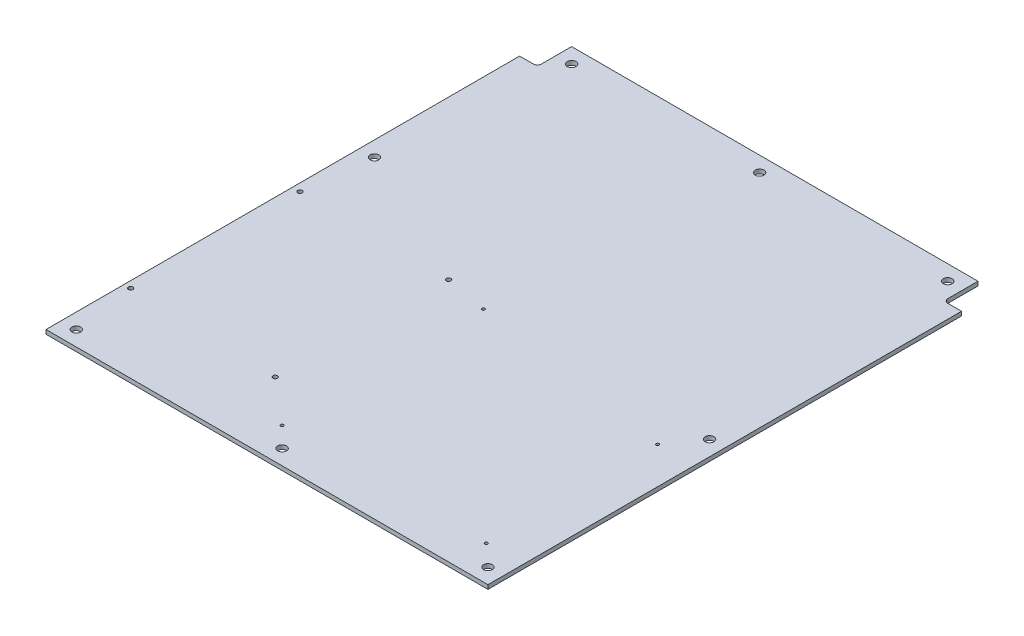
SolidWorks part; units mm, degrees
material "6061-T6 (SS)"
ref_plane "Front" through (0, 0, 0) normal (0, 0, 1) x (1, 0, 0)
ref_plane "Top" through (0, 0, 0) normal (0, 1, 0) x (1, 0, 0)
ref_plane "Right" through (0, 0, 0) normal (1, 0, 0) x (0, 0, -1)
sketch "Sketch1" plane through (0, 0, 0) normal (0, 1, 0) x (1, 0, 0)
  line L1 (170.434, -195.834) -> (-170.434, -195.834)
  line L2 (170.434, -195.834) -> (170.434, 195.834)
  line L3 (170.434, 195.834) -> (-170.434, 195.834)
  line L4 (-170.434, -195.834) -> (-170.434, 195.834)
  line L5 (170.434, -195.834) -> (-170.434, 195.834) construction
  line L6 (170.434, 195.834) -> (-170.434, -195.834) construction
  point P0 (0, 0)
  dimension "D1" = 340.868
  dimension "D2" = 391.668
extrude "Boss-Extrude1" add sketch "Sketch1" along normal blind 3.175
sketch "Sketch2" plane through (0, 3.175, 0) normal (0, 1, 0) x (1, 0, 0)
  line L0 (170.434, 195.834) -> (-170.434, 195.834) construction
  line L1 (-170.434, 195.834) -> (-156.718, 195.834)
  line L2 (-170.434, 195.834) -> (-170.434, 169.418)
  line L3 (-170.434, 169.418) -> (-159.893, 169.418)
  line L4 (-156.718, 195.834) -> (-156.718, 172.593)
  line L5 (170.434, 195.834) -> (156.718, 195.834)
  line L6 (170.434, 195.834) -> (170.434, 169.418)
  line L7 (170.434, 169.418) -> (159.893, 169.418)
  line L8 (156.718, 195.834) -> (156.718, 172.593)
  arc A0 (-156.718, 172.593) -> (-159.893, 169.418) centre (-159.893, 172.593) cw
  arc A1 (156.718, 172.593) -> (159.893, 169.418) centre (159.893, 172.593) ccw
  dimension "D1" = 3.175
  dimension "D2" = 26.416
  dimension "D3" = 13.716
extrude "Cut-Extrude1" cut sketch "Sketch2" against normal blind 10
hole_wizard "1/4 Clearance Hole1" positions "Sketch3" profile "Sketch4" hole size "1/4" standard "ANSI Inch"
sketch "Sketch3" plane through (0, 3.175, 0) normal (0, 1, 0) x (1, 0, 0)
  line L0 (158.75, -184.15) -> (0, -184.15) construction
  line L1 (0, -184.15) -> (-158.75, -184.15) construction
  line L2 (-158.75, -184.15) -> (-158.75, -13.208) construction
  line L3 (-158.75, -13.208) -> (-158.75, 157.734) construction
  line L4 (-158.75, 157.734) -> (158.75, 157.734) construction
  line L5 (158.75, 157.734) -> (158.75, -13.208) construction
  line L6 (158.75, -13.208) -> (158.75, -184.15) construction
  line L8 (145.034, 184.15) -> (0, 184.15) construction
  line L9 (0, 184.15) -> (-145.034, 184.15) construction
  line L10 (-145.034, 184.15) -> (-156.718, 195.834) construction
  line L12 (156.718, 195.834) -> (145.034, 184.15) construction
  line L14 (-158.75, 157.734) -> (-170.434, 169.418) construction
  line L16 (-158.75, -184.15) -> (-170.434, -195.834) construction
  line L18 (158.75, 157.734) -> (170.434, 169.418) construction
  line L20 (158.75, -184.15) -> (170.434, -195.834) construction
  line L21 (158.75, -184.15) -> (158.75, -195.834) construction
  line L22 (-170.434, -195.834) -> (170.434, -195.834) construction
  line L24 (158.75, -184.15) -> (170.434, -184.15) construction
  line L25 (170.434, -195.834) -> (170.434, 169.418) construction
  line L26 (156.718, 195.834) -> (-156.718, 195.834) construction
  point P0 (158.75, -184.15)
  point P2 (-158.75, -184.15)
  point P12 (158.75, -13.208)
  point P14 (0, -184.15)
  point P18 (0, 184.15)
  point P94 (-145.034, 184.15)
  point P96 (145.034, 184.15)
  point P104 (-158.75, 45.834)
  point P107 (0, 0)
  dimension "D1" = 11.684
  dimension "D2" = 150
sketch "Sketch4" plane through (158.75, 3.175, 184.15) normal (1, 0, 0) x (0, 0, 1)
  line L0 (0, 0) -> (0, 20.7798)
  line L1 (0, 20.7798) -> (3.3782, 18.75)
  line L2 (3.3782, 18.75) -> (3.3782, 0)
  line L5 (3.3782, 0) -> (0, 0)
  line L10 (0, 20.7798) -> (-3.3782, 18.75) construction
  line L11 (0, -6.35) -> (0, 107.95) construction
  dimension "Hole Dia." = 6.7564
  dimension "Hole Depth" = 18.75
  dimension "Drill Angle" = 118
hole_wizard "#4-40 Tapped Hole1" positions "Sketch5" profile "Sketch6" tap size "#4-40" standard "ANSI Inch"
sketch "Sketch5" plane through (0, 3.175, 0) normal (0, 1, 0) x (1, 0, 0)
  point P0 (-15.34, -13.51)
  point P3 (142.14, -36.73)
  point P6 (142.14, -168.81)
  point P9 (-15.34, -168.81)
sketch "Sketch6" plane through (-15.34, 3.175, 13.51) normal (1, 0, 0) x (0, 0, 1)
  line L0 (0, 0) -> (0, 8.2792)
  line L1 (0, 8.2792) -> (1.1303, 7.6)
  line L2 (1.1303, 7.6) -> (1.1303, 0)
  line L5 (1.1303, 0) -> (0, 0)
  line L10 (0, 8.2792) -> (-1.1303, 7.6) construction
  line L11 (0, -6.35) -> (0, 107.95) construction
  dimension "Tap Drill Dia." = 2.2606
  dimension "Tap Drill Depth" = 7.6
  dimension "Drill Angle" = 118
cosmetic thread "Hole Thread1" parameters "D1"=3.175, "D2"=2.8448
cosmetic thread "Hole Thread2" parameters "D1"=3.175, "D2"=2.8448
cosmetic thread "Hole Thread3" parameters "D1"=3.175, "D2"=2.8448
cosmetic thread "Hole Thread4" parameters "D1"=3.175, "D2"=2.8448
hole_wizard "#8-32 Tapped Hole1" positions "Sketch7" profile "Sketch8" tap size "#8-32" standard "ANSI Inch"
sketch "Sketch7" plane through (0, 3.175, 0) normal (0, 1, 0) x (1, 0, 0)
  point P0 (-164.6155, -5.7895)
  point P2 (-165.334, -135.625)
  point P5 (-50.3295, -139.1638)
  point P9 (-48.4575, -7.2651)
sketch "Sketch8" plane through (-164.6155, 3.175, 5.7895) normal (1, 0, 0) x (0, 0, 1)
  line L0 (0, 0) -> (0, 11.7478)
  line L1 (0, 11.7478) -> (1.7272, 10.71)
  line L2 (1.7272, 10.71) -> (1.7272, 0)
  line L5 (1.7272, 0) -> (0, 0)
  line L10 (0, 11.7478) -> (-1.7272, 10.71) construction
  line L11 (0, -6.35) -> (0, 107.95) construction
  dimension "Tap Drill Dia." = 3.4544
  dimension "Tap Drill Depth" = 10.71
  dimension "Drill Angle" = 118
cosmetic thread "Hole Thread5" parameters "D1"=3.175, "D2"=4.1656
cosmetic thread "Hole Thread6" parameters "D1"=3.175, "D2"=4.1656
cosmetic thread "Hole Thread7" parameters "D1"=3.175, "D2"=4.1656
cosmetic thread "Hole Thread8" parameters "D1"=3.175, "D2"=4.1656
